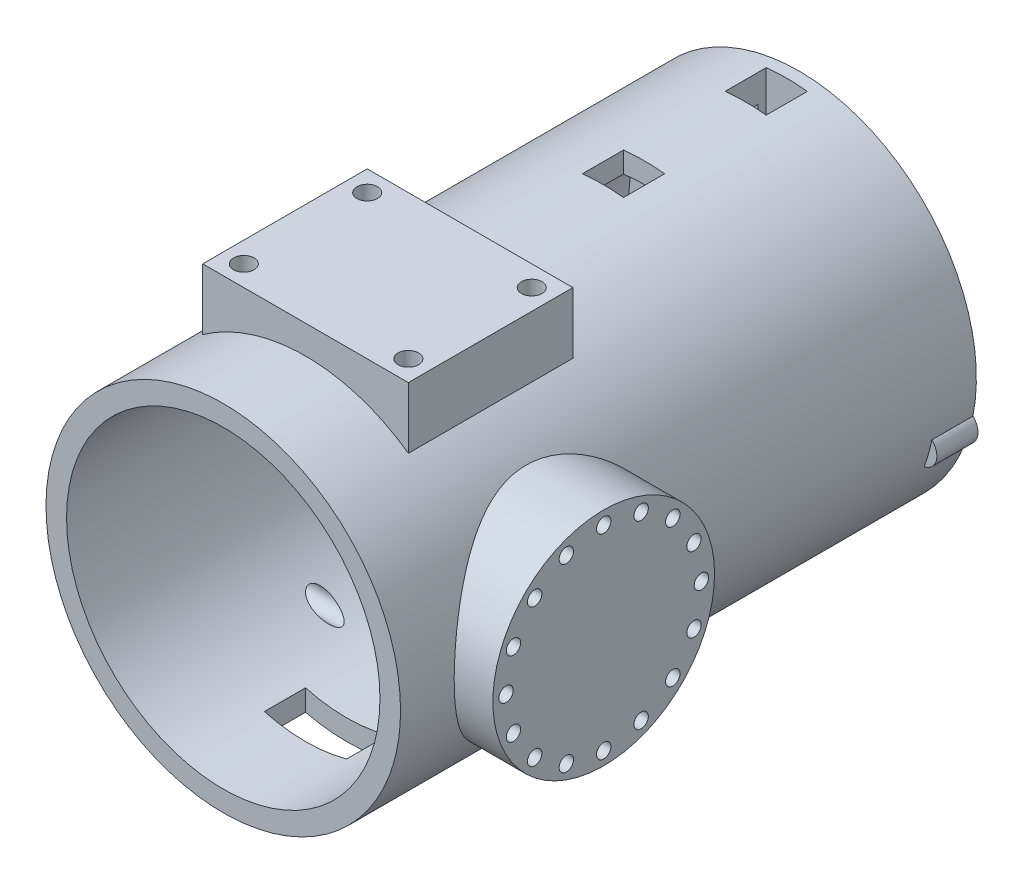
SolidWorks part; units mm, degrees
other "Markup1"
sketch "Sketch14" plane through (-43.1, 43.1, 140) normal (-0.1765, 0.0048, 0.9843) x (0.9842, -0.0149, 0.1765)
other "Markup2"
sketch "Sketch23" plane through (45.1, -43.1, 140) normal (0.9491, -0.0629, 0.3087) x (0.311, 0.031, -0.9499)
ref_plane "Front Plane" through (0, 0, 0) normal (0, 0, 1) x (1, 0, 0)
ref_plane "Top Plane" through (0, 0, 0) normal (0, 1, 0) x (1, 0, 0)
ref_plane "Right Plane" through (0, 0, 0) normal (1, 0, 0) x (0, 0, -1)
sketch "Sketch1" plane through (0, 0, 0) normal (0, 0, 1) x (1, 0, 0)
  circle A1 centre (0, 0) radius 43.1
  dimension "D1" = 86.2
extrude "Main Body" add sketch "Sketch1" along normal blind 140
ref_plane "Plane1" through (0, 43.1, 0) normal (0, 1, 0) x (1, 0, 0)
sketch "Sketch34" plane through (0, 43.1, 0) normal (0, 1, 0) x (1, 0, 0)
  line L6 (-5, -13) -> (5, -13)
  line L8 (-5, -13) -> (-5, -3)
  line L9 (-5, -3) -> (5, -3)
  line L10 (5, -13) -> (5, -3)
  line L11 (-5, -13) -> (5, -3) construction
  line L12 (-5, -3) -> (5, -13) construction
  point P0 (0, -8)
  point P5 (0, 0)
  dimension "D1" = 8
  dimension "D2" = 10
  dimension "D3" = 10
sketch "Sketch6" plane through (0, 43.1, 0) normal (0, 1, 0) x (1, 0, 0)
  line L2 (-5, -47.7) -> (5, -47.7)
  line L3 (-5, -47.7) -> (-5, -37.7)
  line L4 (-5, -37.7) -> (5, -37.7)
  line L5 (5, -47.7) -> (5, -37.7)
  line L6 (-5, -47.7) -> (5, -37.7) construction
  line L7 (-5, -37.7) -> (5, -47.7) construction
  point P2 (0, -42.7)
  dimension "D2" = 10
  dimension "D1" = 42.7
  dimension "D3" = 10
extrude "Cut-Extrude3" cut sketch "Sketch6" against normal through all
ref_plane "Plane2" through (52.5, 0, 0) normal (1, 0, 0) x (0, 0, -1)
sketch "Sketch8" plane through (52.5, 0, 0) normal (1, 0, 0) x (0, 0, -1)
  circle A0 centre (-100, 0) radius 26.95
  dimension "D1" = 53.9
  dimension "D2" = 100
extrude "Boss-Extrude2" add sketch "Sketch8" against normal blind 20
mirror "Mirror1" [suppressed] about plane through (0, 0, 0) normal (1, 0, 0)
ref_plane "Plane3" through (0, 50, 0) normal (0, 1, 0) x (1, 0, 0)
sketch "Sketch33" plane through (0, 50, 0) normal (0, 1, 0) x (1, 0, 0)
  line L1 (-25, -120) -> (25, -120)
  line L2 (-25, -120) -> (-25, -80)
  line L3 (-25, -80) -> (25, -80)
  line L4 (25, -120) -> (25, -80)
  line L5 (-25, -120) -> (25, -80) construction
  line L6 (-25, -80) -> (25, -120) construction
  point P0 (0, -100)
  dimension "D1" = 100
  dimension "D2" = 40
  dimension "D3" = 50
extrude "Boss-Extrude11" add sketch "Sketch33" against normal blind 22
sketch "Sketch35" plane through (0, 50, 0) normal (0, 1, 0) x (1, 0, 0)
  line L0 (-25, -120) -> (-25, -80) construction
  line L1 (25, -120) -> (25, -80) construction
  line L2 (25, -80) -> (-25, -80) construction
  line L3 (-25, -120) -> (25, -120) construction
  circle A0 centre (-20, -85) radius 2.5
  circle A1 centre (20, -85) radius 2.5
  circle A2 centre (-20, -115) radius 2.5
  circle A3 centre (20, -115) radius 2.5
  point P8 (0, 0)
  point P9 (0, 0)
  point P10 (0, 0)
  point P11 (0, 0)
  dimension "D1" = 5
  dimension "D2" = 5
  dimension "D3" = 5
  dimension "D4" = 5
  dimension "D5" = 5
extrude "Cut-Extrude14" cut sketch "Sketch35" against normal blind 26
sketch "Sketch5" plane through (0, 0, 140) normal (0, 0, 1) x (1, 0, 0)
  circle A0 centre (0, 0) radius 31.75
  dimension "D1" = 63.5
extrude "Hole 1" cut sketch "Sketch5" against normal through all
sketch "Sketch10" plane through (0, 0, 0) normal (0, 1, 0) x (1, 0, 0)
  line L0 (43.1, 0) -> (-43.1, 0) construction
  line L1 (-10, -120) -> (10, -120)
  line L2 (-10, -120) -> (-10, -110)
  line L3 (-10, -110) -> (10, -110)
  line L4 (10, -120) -> (10, -110)
  line L5 (-10, -120) -> (10, -110) construction
  line L6 (-10, -110) -> (10, -120) construction
  point P0 (0, -115)
  point P7 (-10, -115)
  dimension "D1" = 110
  dimension "D2" = 10
  dimension "D3" = 20
extrude "Motor Wire Hole" cut sketch "Sketch10" against normal through all
sketch "Sketch27" plane through (0, 0, 0) normal (1, 0, 0) x (0, 0, -1)
  line L1 (-100, -36.5) -> (-60, -36.5)
  line L2 (-100, -36.5) -> (-100, -27.5)
  line L3 (-100, -27.5) -> (-60, -27.5)
  line L4 (-60, -36.5) -> (-60, -27.5)
  dimension "D1" = 60
  dimension "D2" = 27.5
  dimension "D3" = 40
  dimension "D4" = 9
extrude "Boss-Extrude9" add sketch "Sketch27" along normal blind 33 and the other way blind 33
sketch "Sketch11" plane through (0, 0, 0) normal (1, 0, 0) x (0, 0, -1)
  circle A0 centre (-65, -32) radius 2.5
  circle A1 centre (-95, -32) radius 2.5
  dimension "D3" = 5
  dimension "D1" = 65
  dimension "D2" = 32
  dimension "D4" = 30
extrude "Cut-Extrude6" cut sketch "Sketch11" against normal through all both and the other way through all
sketch "Sketch28" plane through (-33, 0, 0) normal (-1, 0, 0) x (0, 0, 1)
  line L0 (62.9793, -28.5) -> (67.0207, -28.5)
  line L1 (67.0207, -28.5) -> (69.0415, -32)
  line L2 (69.0415, -32) -> (67.0207, -35.5)
  line L3 (67.0207, -35.5) -> (62.9793, -35.5)
  line L4 (62.9793, -35.5) -> (60.9585, -32)
  line L6 (60.9585, -32) -> (62.9793, -28.5)
  line L7 (92.9793, -28.5) -> (97.0207, -28.5)
  line L8 (97.0207, -28.5) -> (99.0415, -32)
  line L9 (99.0415, -32) -> (97.0207, -35.5)
  line L10 (97.0207, -35.5) -> (92.9793, -35.5)
  line L11 (92.9793, -35.5) -> (90.9585, -32)
  line L12 (90.9585, -32) -> (92.9793, -28.5)
  circle A0 centre (65, -32) radius 3.5 construction
  circle A1 centre (65, -32) radius 2.5 construction
  circle A2 centre (95, -32) radius 3.5 construction
  circle A3 centre (95, -32) radius 2.5 construction
  dimension "D1" = 7
  dimension "D2" = 7
extrude "Cut-Extrude7" cut sketch "Sketch28" against normal blind 3
sketch "Sketch29" plane through (33, 0, 0) normal (1, 0, 0) x (0, 0, -1)
  circle A0 centre (-95, -32) radius 3.5
  circle A1 centre (-65, -32) radius 3.5
  dimension "D1" = 7
extrude "Cut-Extrude8" cut sketch "Sketch29" against normal blind 4
sketch "Sketch2" plane through (0, 0, 140) normal (0, 0, 1) x (1, 0, 0)
  circle A0 centre (0, 0) radius 38.1
  dimension "D1" = 76.2
extrude "Cut-Extrude5" cut sketch "Sketch2" against normal blind 135
sketch "Sketch9" plane through (0, 0, 5) normal (0, 0, 1) x (1, 0, 0)
  circle A0 centre (0, 0) radius 38.1
  circle A1 centre (0, 0) radius 36.44
  dimension "D1" = 76.2
  dimension "D2" = 1.66
extrude "Boss-Extrude3" add sketch "Sketch9" along normal blind 10
extrude "Cut-Extrude13" cut sketch "Sketch34" against normal blind 15
sketch "Sketch30" plane through (52.5, 0, 0) normal (1, 0, 0) x (0, 0, -1)
  line L0 (-100, 23.75) -> (-100, 0) construction
  circle A0 centre (-100, 0) radius 23.75 construction
  circle A1 centre (-100, 23.75) radius 1.75
  circle A2 centre (-90.9113, 21.9421) radius 1.75
  circle A3 centre (-83.2062, 16.7938) radius 1.75
  circle A4 centre (-78.0579, 9.0887) radius 1.75
  circle A5 centre (-76.25, 0) radius 1.75
  circle A6 centre (-78.0579, -9.0887) radius 1.75
  circle A7 centre (-83.2062, -16.7938) radius 1.75
  circle A8 centre (-90.9113, -21.9421) radius 1.75
  circle A9 centre (-100, -23.75) radius 1.75
  circle A10 centre (-109.0887, -21.9421) radius 1.75
  circle A11 centre (-116.7938, -16.7938) radius 1.75
  circle A12 centre (-121.9421, -9.0887) radius 1.75
  circle A13 centre (-123.75, 0) radius 1.75
  circle A14 centre (-121.9421, 9.0887) radius 1.75
  circle A15 centre (-116.7938, 16.7938) radius 1.75
  circle A16 centre (-109.0887, 21.9421) radius 1.75
  point P38 (-100, 0)
  dimension "D1" = 47.5
  dimension "D2" = 3.5
  dimension "D3" = 16
extrude "Cut-Extrude9" cut sketch "Sketch30" against normal up to surface (22.7083 mm away) up to face at (38.1, 0, 15)
sketch "Sketch31" plane through (52.5, 0, 0) normal (1, 0, 0) x (0, 0, -1)
  line L0 (0, -43.1) -> (0, 43.1) construction
  line L1 (0, -15) -> (-10, -15)
  line L2 (0, -15) -> (0, -7.5)
  line L3 (0, -7.5) -> (-10, -7.5)
  line L4 (-10, -15) -> (-10, -7.5)
  dimension "D1" = 15
  dimension "D2" = 7.5
  dimension "D3" = 10
extrude "Boss-Extrude10" add sketch "Sketch31" against normal up to body from offset 9 offset against normal yes
sketch "Sketch32" plane through (0, 0, 0) normal (0, 0, -1) x (-1, 0, 0)
  line L0 (-43.5, -11.25) -> (-29.6901, -11.25) construction
  line L1 (-43.5, -15) -> (-43.5, -7.5) construction
  line L3 (-42.4424, -7.5) -> (-43.5, -7.5) construction
  line L5 (-43.5, -15) -> (-43.5, -7.5)
  line L6 (-43.5, -7.5) -> (-42.4424, -7.5)
  circle A0 centre (0, 0) radius 31.75 construction
  arc A2 (-40.4056, -15) -> (-42.4424, -7.5) centre (0, 0) ccw construction
  arc A3 (-40.4056, -15) -> (-42.2658, -8.4385) centre (-39.6806, -11.25) cw
  arc A4 (-42.2658, -8.4385) -> (-42.4424, -7.5) centre (0, 0) cw
  line M3 (-42.4424, -7.5) -> (-43.5, -7.5)
  line M4 (-43.5, -7.5) -> (-43.5, -15)
  line M5 (-43.5, -15) -> (-40.4056, -15)
extrude "Cut-Extrude10" cut sketch "Sketch32" against normal up to surface (10 mm away) contours M4 M3 | L5 M5 region at (43.0347, -8.5479, 0) region at (42.7123, -14.1508, 0) up to face at (42.5043, -11.2615, 10)
